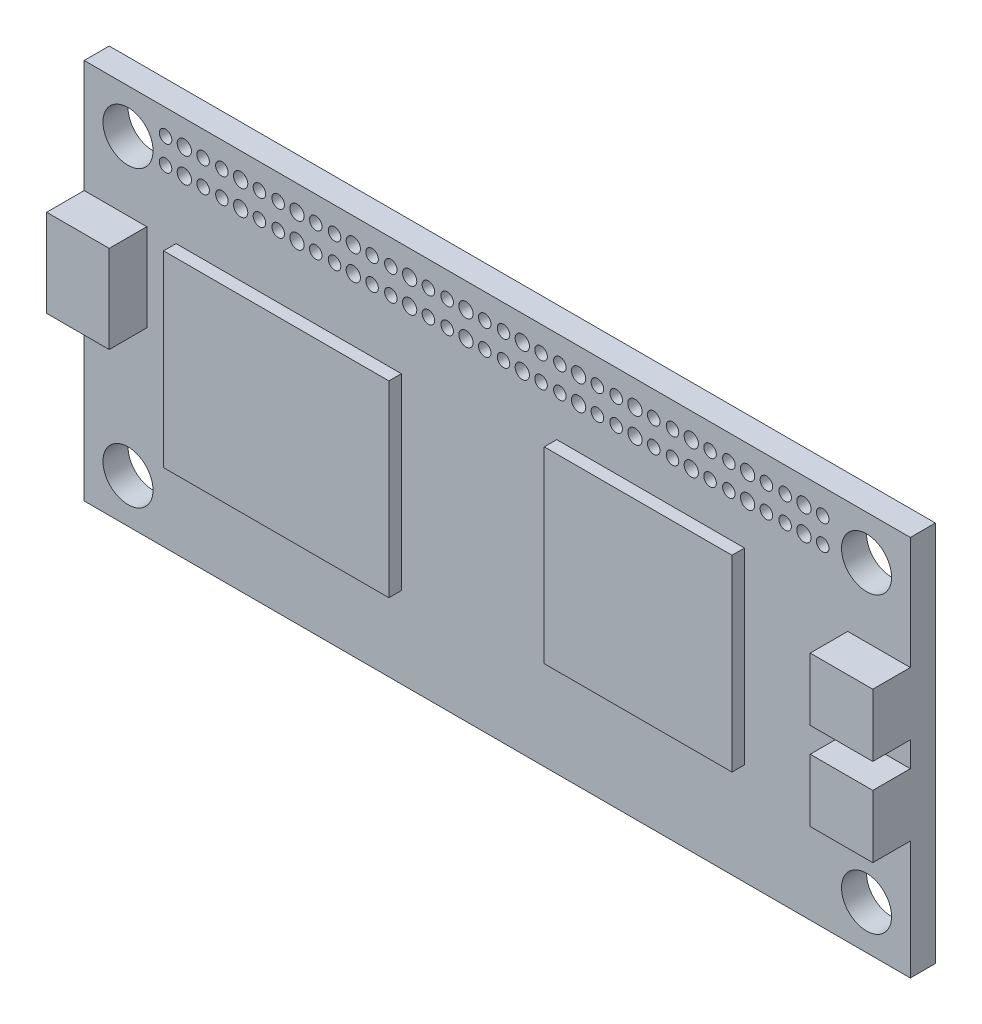
SolidWorks part; units mm, degrees
ref_plane "Front Plane" through (0, 0, 0) normal (0, 0, 1) x (1, 0, 0)
ref_plane "Top Plane" through (0, 0, 0) normal (0, 1, 0) x (1, 0, 0)
ref_plane "Right Plane" through (0, 0, 0) normal (1, 0, 0) x (0, 0, -1)
sketch "Sketch1" plane through (0, 0, 0) normal (0, 0, 1) x (1, 0, 0)
  line L0 (-62.5, 7.3563) -> (-62.5, -23.1237)
  line L1 (-62.5, -23.1237) -> (3.5, -23.1237)
  line L2 (3.5, -23.1237) -> (3.5, 7.3563)
  line L3 (3.5, 7.3563) -> (-62.5, 7.3563)
  line L4 (-62.5, -1.6437) -> (-57.5, -1.6437)
  line L5 (-57.5, -1.6437) -> (-57.5, -8.6437)
  line L6 (-57.5, -8.6437) -> (-62.5, -8.6437)
  line L7 (-24.7477, 0) -> (-9.7477, 0)
  line L8 (-24.7477, 0) -> (-24.7477, -15)
  line L9 (-9.7477, 0) -> (-9.7477, -15)
  line L10 (-9.7477, -15) -> (-24.7477, -15)
  line L11 (-55.1573, -1.6437) -> (-55.1573, -16.6437)
  line L12 (-55.1573, -16.6437) -> (-37.1573, -16.6437)
  line L13 (-37.1573, -16.6437) -> (-37.1573, -1.6437)
  line L14 (-37.1573, -1.6437) -> (-55.1573, -1.6437)
  line L15 (3.5, -1.6437) -> (-1.5, -1.6437)
  line L16 (-1.5, -1.6437) -> (-1.5, -6.6437)
  line L17 (-1.5, -6.6437) -> (3.5, -6.6437)
  line L18 (3.5, -8.6437) -> (-1.5, -8.6437)
  line L19 (-1.5, -8.6437) -> (-1.5, -13.6437)
  line L20 (-1.5, -13.6437) -> (3.5, -13.6437)
  circle A0 centre (-20, 5.3563) radius 0.5
  circle A1 centre (-17, 5.3563) radius 0.5
  circle A2 centre (-18.5, 5.3563) radius 0.5706
  circle A3 centre (-15.5, 5.3563) radius 0.5
  circle A4 centre (-12.5, 5.3563) radius 0.5
  circle A5 centre (-14, 5.3563) radius 0.5706
  circle A6 centre (-11, 5.3563) radius 0.5
  circle A7 centre (-8, 5.3563) radius 0.5
  circle A8 centre (-9.5, 5.3563) radius 0.5706
  circle A9 centre (-6.5, 5.3563) radius 0.5
  circle A10 centre (-3.5, 5.3563) radius 0.5
  circle A11 centre (-5, 5.3563) radius 0.5706
  circle A12 centre (-29, 5.3563) radius 0.5
  circle A13 centre (-26, 5.3563) radius 0.5
  circle A14 centre (-27.5, 5.3563) radius 0.5706
  circle A15 centre (-24.5, 5.3563) radius 0.5
  circle A16 centre (-21.5, 5.3563) radius 0.5
  circle A17 centre (-23, 5.3563) radius 0.5706
  circle A18 centre (-47, 5.3563) radius 0.5
  circle A19 centre (-44, 5.3563) radius 0.5
  circle A20 centre (-45.5, 5.3563) radius 0.5706
  circle A21 centre (-42.5, 5.3563) radius 0.5
  circle A22 centre (-39.5, 5.3563) radius 0.5
  circle A23 centre (-41, 5.3563) radius 0.5706
  circle A24 centre (-38, 5.3563) radius 0.5
  circle A25 centre (-35, 5.3563) radius 0.5
  circle A26 centre (-36.5, 5.3563) radius 0.5706
  circle A27 centre (-33.5, 5.3563) radius 0.5
  circle A28 centre (-30.5, 5.3563) radius 0.5
  circle A29 centre (-32, 5.3563) radius 0.5706
  circle A30 centre (-56, 5.3563) radius 0.5
  circle A31 centre (-53, 5.3563) radius 0.5
  circle A32 centre (-54.5, 5.3563) radius 0.5706
  circle A33 centre (-51.5, 5.3563) radius 0.5
  circle A34 centre (-48.5, 5.3563) radius 0.5
  circle A35 centre (-50, 5.3563) radius 0.5706
  circle A36 centre (-20, 3.3563) radius 0.5
  circle A37 centre (-17, 3.3563) radius 0.5
  circle A38 centre (-18.5, 3.3563) radius 0.5706
  circle A39 centre (-15.5, 3.3563) radius 0.5
  circle A40 centre (-12.5, 3.3563) radius 0.5
  circle A41 centre (-14, 3.3563) radius 0.5706
  circle A42 centre (-11, 3.3563) radius 0.5
  circle A43 centre (-8, 3.3563) radius 0.5
  circle A44 centre (-9.5, 3.3563) radius 0.5706
  circle A45 centre (-6.5, 3.3563) radius 0.5
  circle A46 centre (-3.5, 3.3563) radius 0.5
  circle A47 centre (-5, 3.3563) radius 0.5706
  circle A48 centre (-29, 3.3563) radius 0.5
  circle A49 centre (-26, 3.3563) radius 0.5
  circle A50 centre (-27.5, 3.3563) radius 0.5706
  circle A51 centre (-24.5, 3.3563) radius 0.5
  circle A52 centre (-21.5, 3.3563) radius 0.5
  circle A53 centre (-23, 3.3563) radius 0.5706
  circle A54 centre (-47, 3.3563) radius 0.5
  circle A55 centre (-44, 3.3563) radius 0.5
  circle A56 centre (-45.5, 3.3563) radius 0.5706
  circle A57 centre (-42.5, 3.3563) radius 0.5
  circle A58 centre (-39.5, 3.3563) radius 0.5
  circle A59 centre (-41, 3.3563) radius 0.5706
  circle A60 centre (-38, 3.3563) radius 0.5
  circle A61 centre (-35, 3.3563) radius 0.5
  circle A62 centre (-36.5, 3.3563) radius 0.5706
  circle A63 centre (-33.5, 3.3563) radius 0.5
  circle A64 centre (-30.5, 3.3563) radius 0.5
  circle A65 centre (-32, 3.3563) radius 0.5706
  circle A66 centre (-56, 3.3563) radius 0.5
  circle A67 centre (-53, 3.3563) radius 0.5
  circle A68 centre (-54.5, 3.3563) radius 0.5706
  circle A69 centre (-51.5, 3.3563) radius 0.5
  circle A70 centre (-48.5, 3.3563) radius 0.5
  circle A71 centre (-50, 3.3563) radius 0.5706
  circle A72 centre (-59, 3.8563) radius 2
  circle A73 centre (0, 3.8563) radius 2
  circle A74 centre (0, -19.6237) radius 2
  circle A75 centre (-59, -19.6237) radius 2
  dimension "D1" = 1
  dimension "D8" = 1
  dimension "D15" = 1
  dimension "D20" = 1
  dimension "D29" = 1
  dimension "D34" = 1
  dimension "D80" = 1
  dimension "D85" = 1
  dimension "D92" = 1
  dimension "D97" = 1
  dimension "D106" = 1
  dimension "D111" = 1
  dimension "D170" = 4
  dimension "D173" = 4
  dimension "D178" = 4
  dimension "D182" = 4
  dimension "D2" = 66
  dimension "D3" = 30.48
  dimension "D4" = 0
  dimension "D5" = 0
  dimension "D6" = 1.5
  dimension "D7" = 1.5
  dimension "D9" = 0
  dimension "D10" = 0
  dimension "D11" = 1.5
  dimension "D12" = 1.5
  dimension "D13" = 1.5
  dimension "D14" = 0
  dimension "D16" = 0
  dimension "D17" = 0
  dimension "D18" = 1.5
  dimension "D19" = 1.5
  dimension "D21" = 0
  dimension "D22" = 0
  dimension "D23" = 1.5
  dimension "D24" = 1.5
  dimension "D25" = 1.5
  dimension "D26" = 0
  dimension "D27" = 0
  dimension "D28" = 1.5
  dimension "D30" = 0
  dimension "D31" = 0
  dimension "D32" = 1.5
  dimension "D33" = 1.5
  dimension "D35" = 0
  dimension "D36" = 0
  dimension "D37" = 1.5
  dimension "D38" = 1.5
  dimension "D39" = 1.5
  dimension "D40" = 0
  dimension "D41" = 0
  dimension "D42" = 1.5
  dimension "D43" = 2
  dimension "D44" = 0
  dimension "D45" = 0
  dimension "D46" = 1.5
  dimension "D47" = 1.5
  dimension "D48" = 0
  dimension "D49" = 0
  dimension "D50" = 1.5
  dimension "D51" = 1.5
  dimension "D52" = 1.5
  dimension "D53" = 0
  dimension "D54" = 0
  dimension "D55" = 0
  dimension "D56" = 1.5
  dimension "D57" = 1.5
  dimension "D58" = 0
  dimension "D59" = 0
  dimension "D60" = 1.5
  dimension "D61" = 1.5
  dimension "D62" = 1.5
  dimension "D63" = 0
  dimension "D64" = 0
  dimension "D65" = 1.5
  dimension "D66" = 0
  dimension "D67" = 0
  dimension "D68" = 1.5
  dimension "D69" = 1.5
  dimension "D70" = 0
  dimension "D71" = 0
  dimension "D72" = 1.5
  dimension "D73" = 1.5
  dimension "D74" = 1.5
  dimension "D75" = 0
  dimension "D76" = 0
  dimension "D77" = 1.5
  dimension "D78" = 1.5
  dimension "D79" = 1.5
  dimension "D81" = 0
  dimension "D82" = 0
  dimension "D83" = 1.5
  dimension "D84" = 1.5
  dimension "D86" = 0
  dimension "D87" = 0
  dimension "D88" = 1.5
  dimension "D89" = 1.5
  dimension "D90" = 1.5
  dimension "D91" = 0
  dimension "D93" = 0
  dimension "D94" = 0
  dimension "D95" = 1.5
  dimension "D96" = 1.5
  dimension "D98" = 0
  dimension "D99" = 0
  dimension "D100" = 1.5
  dimension "D101" = 1.5
  dimension "D102" = 1.5
  dimension "D103" = 0
  dimension "D104" = 0
  dimension "D105" = 1.5
  dimension "D107" = 0
  dimension "D108" = 0
  dimension "D109" = 1.5
  dimension "D110" = 1.5
  dimension "D112" = 0
  dimension "D113" = 0
  dimension "D114" = 1.5
  dimension "D115" = 1.5
  dimension "D116" = 1.5
  dimension "D117" = 0
  dimension "D118" = 0
  dimension "D119" = 1.5
  dimension "D120" = 0
  dimension "D121" = 0
  dimension "D122" = 1.5
  dimension "D123" = 1.5
  dimension "D124" = 0
  dimension "D125" = 0
  dimension "D126" = 1.5
  dimension "D127" = 1.5
  dimension "D128" = 1.5
  dimension "D129" = 0
  dimension "D130" = 0
  dimension "D131" = 0
  dimension "D132" = 1.5
  dimension "D133" = 1.5
  dimension "D134" = 0
  dimension "D135" = 0
  dimension "D136" = 1.5
  dimension "D137" = 1.5
  dimension "D138" = 1.5
  dimension "D139" = 0
  dimension "D140" = 0
  dimension "D141" = 1.5
  dimension "D142" = 0
  dimension "D143" = 0
  dimension "D144" = 1.5
  dimension "D145" = 1.5
  dimension "D146" = 0
  dimension "D147" = 0
  dimension "D148" = 1.5
  dimension "D149" = 1.5
  dimension "D150" = 1.5
  dimension "D151" = 0
  dimension "D152" = 0
  dimension "D153" = 1.5
  dimension "D154" = 1.5
  dimension "D155" = 1.5
  dimension "D156" = 2
  dimension "D157" = 0
  dimension "D158" = 7
  dimension "D159" = 9
  dimension "D160" = 7
  dimension "D161" = 5
  dimension "D162" = 15
  dimension "D163" = 15
  dimension "D164" = 18
  dimension "D165" = 15
  dimension "D166" = 5
  dimension "D167" = 5
  dimension "D168" = 5
  dimension "D169" = 5
  dimension "D171" = 3.5
  dimension "D172" = 3.5
  dimension "D174" = 3.5
  dimension "D175" = 3.5
  dimension "D176" = 3.5
  dimension "D177" = 3.5
  dimension "D179" = 2
  dimension "D180" = 9
  dimension "D181" = 3.5
  dimension "D183" = 3.5
extrude "Boss-Extrude1" add sketch "Sketch1" along normal blind 2 contours L20 L19 L18 L2 L17 L16 L15 L3 L0 L4 L5 L6 L1 A75 A74 A73 A72 A71 A70 A69 A68 A67 A66 A65 A64 A63 A62 A61 A60 A59 region at (-28.5155, -8.3506, 0)
extrude "Boss-Extrude2" add sketch "Sketch1<3>" along normal blind 5 contours L6 L5 L4 L0 | L16 L17 L2 L15 | L19 L20 L2 L18 region at (-60, -5.1437, 0) region at (1, -4.1437, 0) region at (1, -11.1437, 0)
sketch "Sketch1<3>" plane through (0, 0, 0) normal (0, 0, 1) x (1, 0, 0) same geometry as "Sketch1"
extrude "Boss-Extrude3" add sketch "Sketch1<4>" along normal blind 3 contours L13 L14 L11 L12 | L10 L9 L7 L8 region at (-17.2477, -7.5, 0) region at (-46.1573, -9.1437, 0)
sketch "Sketch1<4>" plane through (0, 0, 0) normal (0, 0, 1) x (1, 0, 0) same geometry as "Sketch1"
